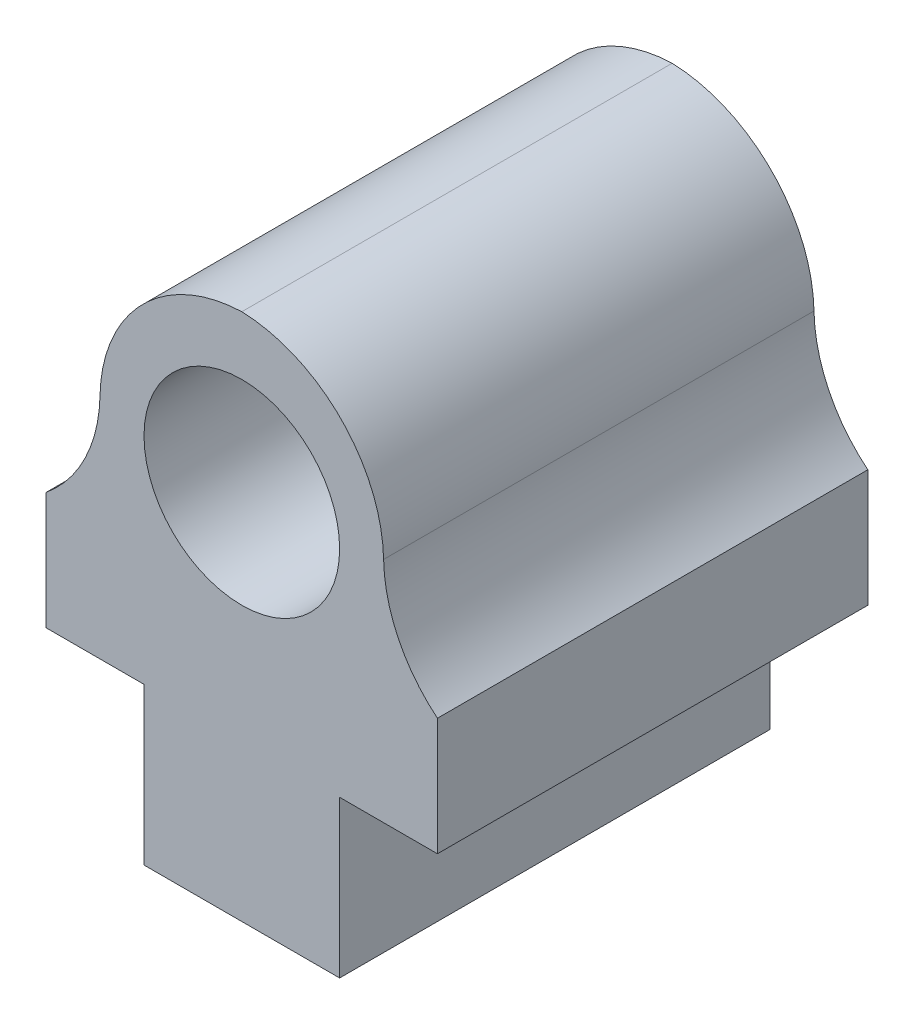
SolidWorks part; units mm, degrees
ref_plane "Front Plane" through (0, 0, 0) normal (0, 0, 1) x (1, 0, 0)
ref_plane "Top Plane" through (0, 0, 0) normal (0, 1, 0) x (1, 0, 0)
ref_plane "Right Plane" through (0, 0, 0) normal (1, 0, 0) x (0, 0, -1)
sketch "Sketch6" plane through (0, 0, 0) normal (0, 1, 0) x (1, 0, 0)
  line L1 (0, 0) -> (20, 0)
  line L2 (0, 0) -> (0, 22)
  line L3 (0, 22) -> (20, 22)
  line L4 (20, 0) -> (20, 22)
  dimension "D1" = 20
  dimension "D2" = 22
extrude "Boss-Extrude5" add sketch "Sketch6" along normal blind 6
sketch "Sketch7" plane through (0, 0, 0) normal (0, -1, 0) x (1, 0, 0)
  line L0 (0, 0) -> (20, 0) construction
  line L1 (5, 0) -> (15, 0)
  line L2 (5, 0) -> (5, -22)
  line L3 (5, -22) -> (15, -22)
  line L4 (15, 0) -> (15, -22)
  line L5 (20, -22) -> (0, -22) construction
  line L6 (0, -22) -> (0, 0) construction
  dimension "D1" = 10
  dimension "D2" = 5
extrude "Boss-Extrude6" add sketch "Sketch7" along normal blind 8
sketch "Sketch8" plane through (0, 6, 0) normal (0, 1, 0) x (1, 0, 0)
  line L0 (20, 22) -> (0, 22) construction
  line L1 (0, 0) -> (20, 0) construction
  line L2 (2.75, 22) -> (17.25, 22)
  line L3 (2.75, 22) -> (2.75, 0)
  line L4 (2.75, 0) -> (17.25, 0)
  line L5 (17.25, 22) -> (17.25, 0)
  line L6 (0, 22) -> (0, 0) construction
  dimension "D1" = 14.5
  dimension "D2" = 2.75
extrude "Boss-Extrude7" add sketch "Sketch8" along normal blind 13
sketch "Sketch9" plane through (0, 0, 0) normal (0, 0, 1) x (1, 0, 0)
  line L0 (2.75, 19) -> (2.75, 6) construction
  line L1 (2.75, 19) -> (17.25, 19) construction
  circle A0 centre (10, 11) radius 5
  dimension "D1" = 7.25
  dimension "D2" = 8
extrude "Cut-Extrude1" cut sketch "Sketch9" against normal through all
fillet "Fillet1" radius 7.5 2 edges at (17.25, 19, -11) (2.75, 19, -11)
fillet "Fillet2" radius 7.5 2 edges at (17.25, 6, -11) (2.75, 6, -11)
